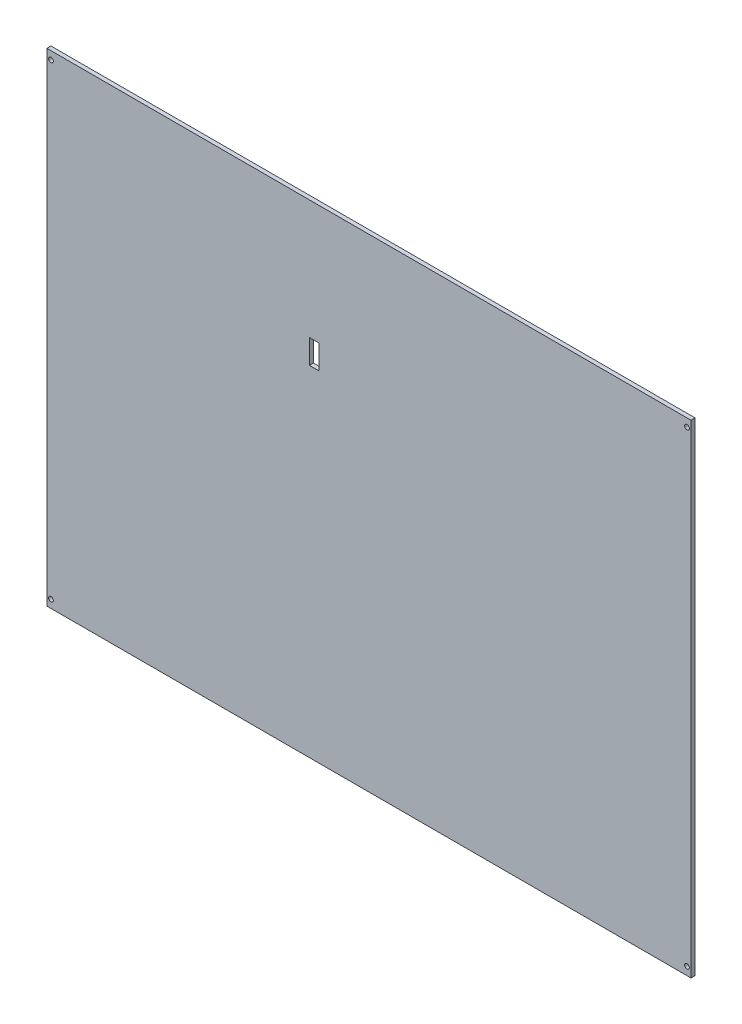
SolidWorks part; units mm, degrees
ref_plane "Front Plane" through (0, 0, 0) normal (0, 0, 1) x (1, 0, 0)
ref_plane "Top Plane" through (0, 0, 0) normal (0, 1, 0) x (1, 0, 0)
ref_plane "Right Plane" through (0, 0, 0) normal (1, 0, 0) x (0, 0, -1)
sketch "Sketch1" plane through (0, 0, 0) normal (0, 0, 1) x (1, 0, 0)
  line L1 (-254, -190.5) -> (254, -190.5)
  line L2 (-254, -190.5) -> (-254, 190.5)
  line L3 (-254, 190.5) -> (254, 190.5)
  line L4 (254, -190.5) -> (254, 190.5)
  line L5 (-254, -190.5) -> (254, 190.5) construction
  line L6 (-254, 190.5) -> (254, -190.5) construction
  point P0 (0, 0)
  dimension "D1" = 508
  dimension "D2" = 381
extrude "Boss-Extrude1" add sketch "Sketch1" along normal blind 3.175
sketch "Sketch2" plane through (0, 0, 3.175) normal (0, 0, 1) x (1, 0, 0)
  line L0 (-250.825, 190.5) -> (-250.825, -190.5) construction
  line L1 (254, 190.5) -> (-254, 190.5) construction
  line L2 (-254, -190.5) -> (254, -190.5) construction
  line L3 (250.825, 190.5) -> (250.825, -190.5) construction
  line L4 (254, -190.5) -> (254, 190.5) construction
  line L5 (-254, 190.5) -> (-254, -190.5) construction
  circle A0 centre (-250.825, -184.15) radius 1.8542
  circle A1 centre (-250.825, 184.15) radius 1.8542
  circle A2 centre (250.825, 184.15) radius 1.8542
  circle A3 centre (250.825, -184.15) radius 1.8542
  dimension "D3" = 3.7084
  dimension "D1" = 3.175
  dimension "D2" = 3.175
  dimension "D4" = 6.35
  dimension "D5" = 6.35
  dimension "D6" = 6.35
  dimension "D7" = 6.35
extrude "Cut-Extrude1" cut sketch "Sketch2" against normal blind 3.175
sketch "Sketch3" plane through (0, 0, 3.175) normal (0, 0, 1) x (1, 0, 0)
  line L0 (-254, 190.5) -> (-254, -190.5) construction
  line L1 (-46.99, 77.47) -> (-39.37, 77.47)
  line L2 (-46.99, 77.47) -> (-46.99, 96.52)
  line L3 (-46.99, 96.52) -> (-39.37, 96.52)
  line L4 (-39.37, 77.47) -> (-39.37, 96.52)
  line L5 (254, 190.5) -> (-254, 190.5) construction
  dimension "D1" = 207.01
  dimension "D2" = 7.62
  dimension "D3" = 113.03
  dimension "D4" = 19.05
extrude "Cut-Extrude2" cut sketch "Sketch3" against normal up to surface (3.175 mm away) up to face at (252.6792, -184.15, 0)
